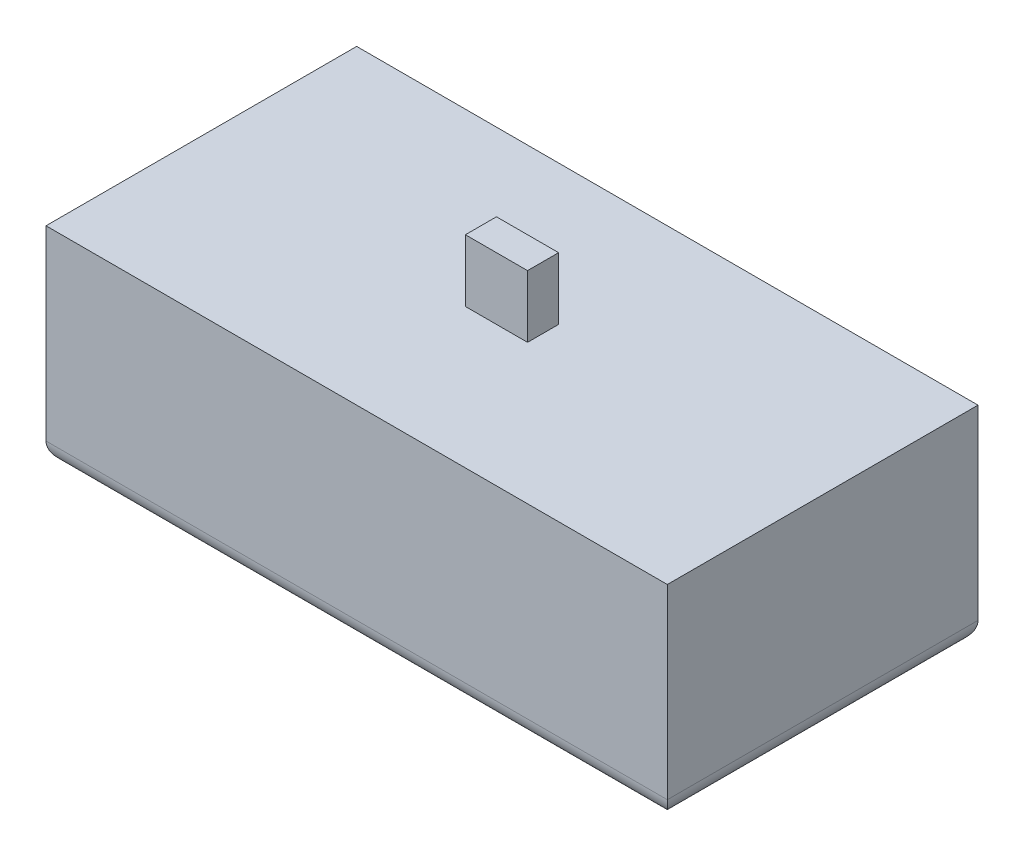
SolidWorks part; units mm, degrees
ref_plane "Front Plane" through (0, 0, 0) normal (0, 0, 1) x (1, 0, 0)
ref_plane "Top Plane" through (0, 0, 0) normal (0, 1, 0) x (1, 0, 0)
ref_plane "Right Plane" through (0, 0, 0) normal (1, 0, 0) x (0, 0, -1)
sketch "Sketch1" plane through (0, 0, 0) normal (0, 1, 0) x (1, 0, 0)
  line L1 (150, 75) -> (-150, 75)
  line L2 (150, 75) -> (150, -75)
  line L3 (150, -75) -> (-150, -75)
  line L4 (-150, 75) -> (-150, -75)
  line L5 (150, 75) -> (-150, -75) construction
  line L6 (150, -75) -> (-150, 75) construction
  point P0 (0, 0)
  dimension "D1" = 300
  dimension "D2" = 150
extrude "Boss-Extrude1" add sketch "Sketch1" along normal blind 100
sketch "Sketch2" plane through (0, 100, 0) normal (0, 1, 0) x (1, 0, 0)
  line L1 (-15, 7.5) -> (15, 7.5)
  line L2 (-15, 7.5) -> (-15, -7.5)
  line L3 (-15, -7.5) -> (15, -7.5)
  line L4 (15, 7.5) -> (15, -7.5)
  line L5 (-15, 7.5) -> (15, -7.5) construction
  line L6 (-15, -7.5) -> (15, 7.5) construction
  point P0 (0, 0)
  dimension "D1" = 15
  dimension "D2" = 30
extrude "Boss-Extrude2" add sketch "Sketch2" along normal blind 30
fillet "Fillet1" radius 10 4 edges at (0, 0, 75) (150, 0, 0) (0, 0, -75) (-150, 0, 0)
